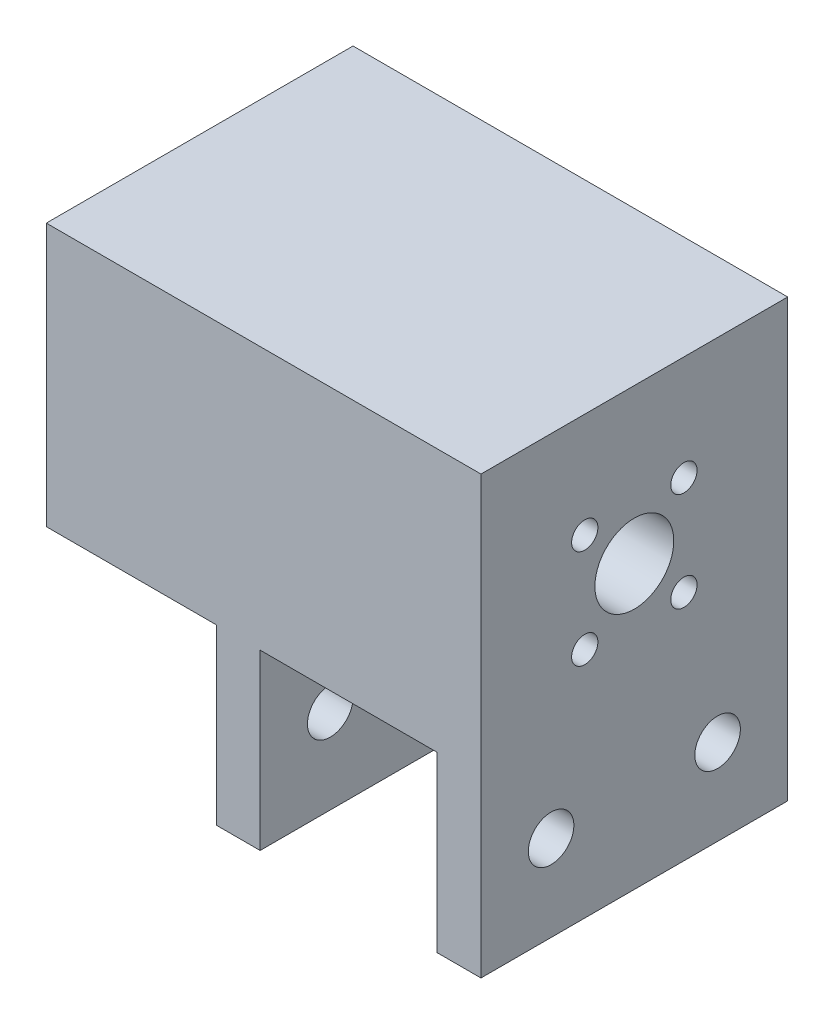
SolidWorks part; units mm, degrees
ref_plane "前视基准面" through (0, 0, 0) normal (0, 0, 1) x (1, 0, 0)
ref_plane "上视基准面" through (0, 0, 0) normal (0, 1, 0) x (1, 0, 0)
ref_plane "右视基准面" through (0, 0, 0) normal (1, 0, 0) x (0, 0, -1)
other "Configuration Table"
sketch "草图1" plane through (0, 0, 0) normal (0, 0, 1) x (1, 0, 0)
  line L0 (0, -39.6057) -> (0, 25.2485) construction
  line L9 (10.1, -34.8) -> (15.1, -34.8)
  line L10 (-24.5, -15) -> (-15.1, -15)
  line L11 (-24.5, -15) -> (-24.5, 15)
  line L12 (-24.5, 15) -> (24.5, 15)
  line L13 (24.5, -15) -> (24.5, 15)
  line L14 (-24.5, -15) -> (24.5, 15) construction
  line L15 (-24.5, 15) -> (24.5, -15) construction
  line L16 (-10.1, -15) -> (10.1, -15)
  line L17 (-15.1, -15) -> (-15.1, -34.8)
  line L18 (-15.1, -34.8) -> (-10.1, -34.8)
  line L19 (15.1, -15) -> (15.1, -34.8)
  line L21 (-10.1, -34.8) -> (-10.1, -15)
  line L22 (-10.1, -15) -> (10.1, -15)
  line L23 (10.1, -34.8) -> (10.1, -15)
  line L24 (-15.3981, -45.5587) -> (10.1, -15) construction
  line L25 (-10.1, -15) -> (18.7639, -49.5924) construction
  line L26 (-10.1, -15) -> (10.1, -15)
  line L27 (15.1, -15) -> (24.5, -15)
  point P2 (0, 0)
  point P12 (0, -27.1045)
  dimension "D1" = 49
  dimension "D2" = 30
  dimension "D3" = 19.8
  dimension "D4" = 5
  dimension "D5" = 20.2
extrude "凸台-拉伸1" add sketch "草图1" along normal blind 35 contours L19 L27 L13 L12 L11 L10 L17 L18 L21 L16 L23 L9 region at (0, -2.9558, 0)
hole_wizard "孔1" positions "草图4" profile "草图3" legacy end condition through all
sketch "草图4" plane through (-24.5, 0, 0) normal (-1, 0, 0) x (0, 0, 1)
  line L0 (17.5, 15) -> (17.5, -15) construction
  line L1 (35, 15) -> (0, 15) construction
  line L2 (35, -15) -> (0, -15) construction
  point P0 (17.5, -2.6)
  dimension "D1" = 12.4
sketch "草图3" plane through (-24.5, -2.6, 17.5) normal (0, 1, 0) x (0, 0, 1)
  line L0 (0, 0) -> (0, 49)
  line L1 (0, 49) -> (4.5, 49)
  line L2 (4.5, 49) -> (4.5, 0)
  line L3 (4.5, 0) -> (0, 0)
  line L4 (0, 110) -> (0, -10) construction
  dimension "直径" = 9
  dimension "深度" = 49
sketch "草图12" plane through (-24.5, 0, 0) normal (-1, 0, 0) x (0, 0, 1)
  line L1 (11.8431, -8.2569) -> (23.1569, -8.2569) construction
  line L2 (11.8431, -8.2569) -> (11.8431, 3.0569) construction
  line L3 (11.8431, 3.0569) -> (23.1569, 3.0569) construction
  line L4 (23.1569, -8.2569) -> (23.1569, 3.0569) construction
  line L5 (11.8431, -8.2569) -> (23.1569, 3.0569) construction
  line L6 (11.8431, 3.0569) -> (23.1569, -8.2569) construction
  circle A0 centre (17.5, -2.6) radius 8 construction
  circle A2 centre (11.8431, 3.0569) radius 1.5
  circle A3 centre (23.1569, 3.0569) radius 1.5
  circle A4 centre (23.1569, -8.2569) radius 1.5
  circle A5 centre (11.8431, -8.2569) radius 1.5
  dimension "D1" = 16
  dimension "D2" = 3
  dimension "D3" = 3
  dimension "D4" = 3
  dimension "D5" = 3
extrude "切除-拉伸1" cut sketch "草图12" against normal through all
sketch "草图15" plane through (-24.5, 0, 0) normal (-1, 0, 0) x (0, 0, 1)
  circle A0 centre (17.5, -2.6) radius 5.2
  dimension "D1" = 10.4
extrude "切除-拉伸4" cut sketch "草图15" against normal blind 16
sketch "草图14" plane through (-24.5, 0, 0) normal (-1, 0, 0) x (0, 0, 1)
  circle A0 centre (17.5, -2.6) radius 11.75
  dimension "D1" = 23.5
extrude "切除-拉伸3" cut sketch "草图14" against normal blind 4
hole_wizard "孔2" positions "草图16" profile "草图17" legacy
sketch "草图16" plane through (-15.1, 0, 0) normal (-1, 0, 0) x (0, 0, 1)
  line L0 (35, -15) -> (0, -15) construction
  line L1 (35, -15) -> (35, -34.8) construction
  line L2 (0, -15) -> (0, -34.8) construction
  point P0 (8, -25)
  point P2 (27, -25)
  dimension "D1" = 10
  dimension "D2" = 10
  dimension "D3" = 8
  dimension "D4" = 8
sketch "草图17" plane through (-15.1, -25, 8) normal (0, 1, 0) x (0, 0, 1)
  line L0 (0, 0) -> (0, 100)
  line L1 (0, 100) -> (2.6, 100)
  line L2 (2.6, 100) -> (2.6, 0)
  line L3 (2.6, 0) -> (0, 0)
  line L4 (0, 110) -> (0, -10) construction
  dimension "直径" = 5.2
  dimension "深度" = 100
sketch "草图18" plane through (-24.5, 0, 0) normal (-1, 0, 0) x (0, 0, 1)
  line L1 (0, 15) -> (35, 15)
  line L2 (0, 15) -> (0, -15)
  line L3 (0, -15) -> (35, -15)
  line L4 (35, 15) -> (35, -15)
  circle A0 centre (17.5, -2.6) radius 11.75
extrude "凸台-拉伸2" add sketch "草图18" along normal blind 10
sketch "草图19" plane through (0, 0, 0) normal (0, 0, -1) x (-1, 0, 0)
  line L1 (-15.1, -15) -> (-24.5, -15)
  line L2 (-15.1, -15) -> (-15.1, 15)
  line L3 (-15.1, 15) -> (-24.5, 15)
  line L4 (-24.5, -15) -> (-24.5, 15)
extrude "切除-拉伸5" cut sketch "草图19" against normal through all
